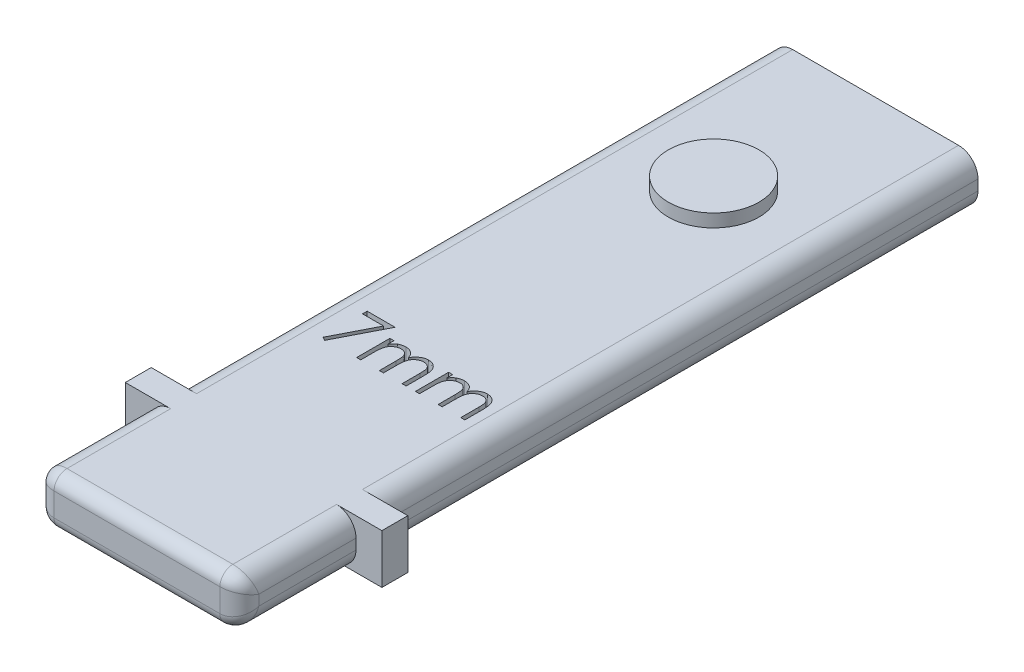
SolidWorks part; units mm, degrees
ref_plane "Front Plane" through (0, 0, 0) normal (0, 0, 1) x (1, 0, 0)
ref_plane "Top Plane" through (0, 0, 0) normal (0, 1, 0) x (1, 0, 0)
ref_plane "Right Plane" through (0, 0, 0) normal (1, 0, 0) x (0, 0, -1)
sketch "Sketch2" plane through (0, 0, 0) normal (0, 1, 0) x (1, 0, 0)
  line L1 (0, 0) -> (15.8, 0)
  line L2 (0, 0) -> (0, 57)
  line L3 (0, 57) -> (15.8, 57)
  line L4 (15.8, 0) -> (15.8, 57)
  dimension "D1" = 57
  dimension "D2" = 15.8
extrude "Boss-Extrude1" add sketch "Sketch2" along normal blind 3.8
fillet "Fillet3" radius 1 2 edges at (7.9, 0, 0) (7.9, 3.8, 0)
sketch "Sketch5" plane through (0, 3.8, 0) normal (0, 1, 0) x (1, 0, 0)
  line L0 (15.8, 57) -> (0, 57) construction
  circle A0 centre (7.9, 44.5) radius 3.5
  point P4 (7.9, 57)
  dimension "D1" = 7
  dimension "D2" = 12.5
extrude "Boss-Extrude4" add sketch "Sketch5" along normal blind 1
sketch "Sketch6" plane through (15.8, 0, 0) normal (1, 0, 0) x (0, 0, -1)
  line L0 (9, 3.8) -> (9, 0)
  line L1 (1, 3.8) -> (57, 3.8) construction
  line L2 (1, 0) -> (57, 0) construction
  line L3 (9, 0) -> (11, 0)
  line L4 (11, 0) -> (11, 3.8)
  line L5 (11, 3.8) -> (9, 3.8)
  line L6 (0, 2.8) -> (0, 1) construction
  dimension "D1" = 9
  dimension "D2" = 2
extrude "Boss-Extrude5" add sketch "Sketch6" along normal blind 2
sketch "Sketch7" plane through (0, 0, 0) normal (-1, 0, 0) x (0, 0, 1)
  line L0 (-57, 0) -> (-1, 0) construction
  line L1 (-9, 0) -> (-11, 0)
  line L2 (-9, 0) -> (-9, 3.8)
  line L3 (-9, 3.8) -> (-11, 3.8)
  line L4 (-11, 0) -> (-11, 3.8)
  line L5 (-57, 3.8) -> (-1, 3.8) construction
  line L6 (0, 2.8) -> (0, 1) construction
  dimension "D1" = 9
  dimension "D2" = 2
extrude "Boss-Extrude6" add sketch "Sketch7" along normal blind 2
fillet "Fillet4" radius 1.5 14 edges at (0, 0.2929, -0.2929) (0, 1.9, 0) (0, 3.5071, -0.2929) (15.8, 0.2929, -0.2929) (15.8, 1.9, 0) (15.8, 3.5071, -0.2929) (0, 0, -34) (0, 0, -5) (0, 3.8, -5) (0, 3.8, -34) (15.8, 0, -34) (15.8, 3.8, -34) (15.8, 0, -5) (15.8, 3.8, -5)
sketch "Sketch9" plane through (0, 3.8, 0) normal (0, 1, 0) x (1, 0, 0)
  text T0 "7mm\r\n\r\n"
extrude "Cut-Extrude1" cut sketch "Sketch9" against normal blind 5
